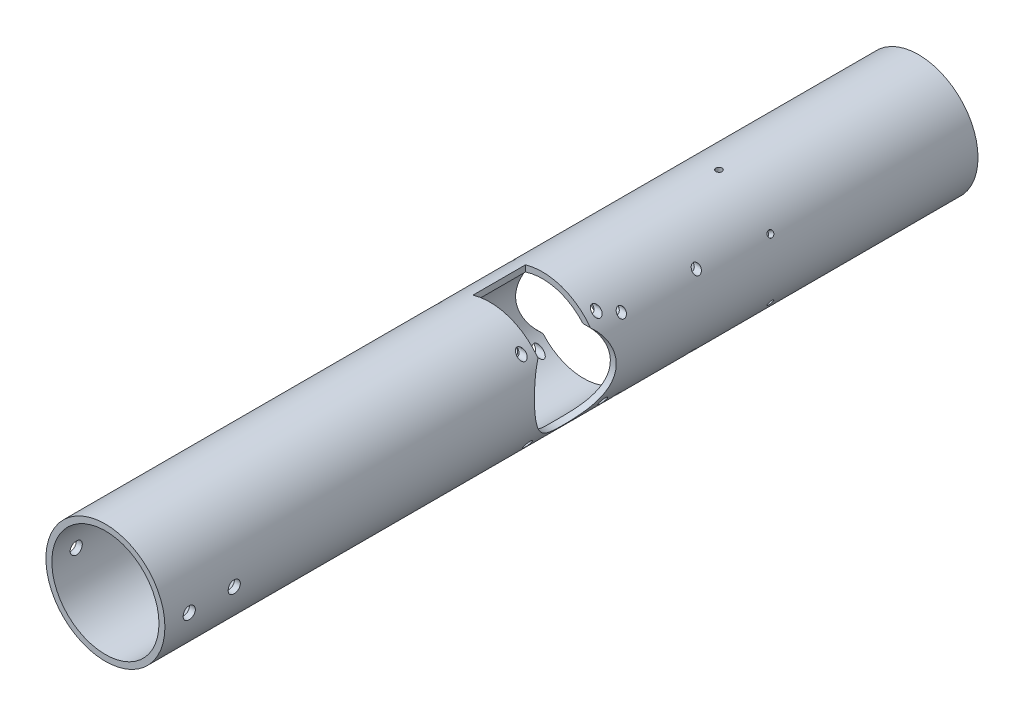
SolidWorks part; units mm, degrees
material "6061-T6 (SS)"
ref_plane "Front Plane" through (0, 0, 0) normal (0, 0, 1) x (1, 0, 0)
ref_plane "Top Plane" through (0, 0, 0) normal (0, 1, 0) x (1, 0, 0)
ref_plane "Right Plane" through (0, 0, 0) normal (1, 0, 0) x (0, 0, -1)
sketch "Sketch1" plane through (0, 0, 0) normal (0, 0, 1) x (1, 0, 0)
  circle A0 centre (0, 0) radius 31.75
  circle A1 centre (0, 0) radius 28.575
  dimension "D1" = 63.5
  dimension "D2" = 57.15
extrude "Boss-Extrude1" add sketch "Sketch1" along normal blind 125 and the other way blind 250 contours A1 | A0
sketch "Sketch2" plane through (0, 0, 0) normal (1, 0, 0) x (0, 0, -1)
  circle A2 centre (73.488, -2) radius 21.75
  dimension "D1" = 43.5
  dimension "D2" = 73.488
  dimension "D3" = 2
extrude "Cut-Extrude1" cut sketch "Sketch2" against normal through all
sketch "Sketch3" plane through (0, 0, 0) normal (1, 0, 0) x (0, 0, -1)
  circle A1 centre (23.45, 2) radius 21.75
  dimension "D1" = 23.45
  dimension "D2" = 43.5
  dimension "D3" = 2
extrude "Cut-Extrude2" cut sketch "Sketch3" along normal through all
sketch "Sketch5" plane through (0, 0, 0) normal (1, 0, 0) x (0, 0, -1)
  line L1 (87.488, -12.75) -> (59.488, -12.75)
  line L2 (87.488, -12.75) -> (87.488, -34.75)
  line L3 (87.488, -34.75) -> (59.488, -34.75)
  line L4 (59.488, -12.75) -> (59.488, -34.75)
  line L5 (87.488, -12.75) -> (59.488, -34.75) construction
  line L6 (87.488, -34.75) -> (59.488, -12.75) construction
  circle A0 centre (73.488, -2) radius 21.75 construction
  circle A1 centre (73.488, -2) radius 21.75 construction
  circle A2 centre (73.488, -2) radius 21.75 construction
  point P0 (73.488, -23.75)
  dimension "D1" = 28
  dimension "D2" = 22
extrude "Cut-Extrude4" cut sketch "Sketch5" against normal through all from offset 9
sketch "Sketch6" plane through (0, 0, 0) normal (1, 0, 0) x (0, 0, -1)
  line L1 (9.45, 34.75) -> (37.45, 34.75)
  line L2 (9.45, 34.75) -> (9.45, 12.75)
  line L3 (9.45, 12.75) -> (37.45, 12.75)
  line L4 (37.45, 34.75) -> (37.45, 12.75)
  line L5 (9.45, 34.75) -> (37.45, 12.75) construction
  line L6 (9.45, 12.75) -> (37.45, 34.75) construction
  circle A0 centre (23.45, 2) radius 21.75 construction
  circle A1 centre (23.45, 2) radius 21.75 construction
  circle A2 centre (23.45, 2) radius 21.75 construction
  point P0 (23.45, 23.75)
  dimension "D1" = 28
  dimension "D2" = 22
extrude "Cut-Extrude5" cut sketch "Sketch6" along normal through all from offset 9 offset against normal yes
sketch "Sketch10" plane through (0, 0, 0) normal (1, 0, 0) x (0, 0, -1)
  line L1 (113.488, 38) -> (33.488, 38)
  line L2 (113.488, 38) -> (113.488, -42)
  line L3 (113.488, -42) -> (33.488, -42)
  line L4 (33.488, 38) -> (33.488, -42)
  line L5 (113.488, 38) -> (33.488, -42) construction
  line L6 (113.488, -42) -> (33.488, 38) construction
  point P0 (73.488, -2)
  dimension "D1" = 80
  dimension "D2" = 80
sketch "Sketch11" plane through (0, 0, 0) normal (1, 0, 0) x (0, 0, -1)
  line L0 (113.488, 38) -> (33.488, -42) construction
  line L1 (113.488, -42) -> (33.488, 38) construction
  line L2 (51.738, -2) -> (95.238, -2) construction
  line L3 (53.488, 18) -> (53.488, -22) construction
  circle A0 centre (93.488, 18) radius 2
  circle A1 centre (53.488, 18) radius 2
  circle A2 centre (53.488, -22) radius 2
  circle A3 centre (93.488, -22) radius 2
  arc A4 (87.488, -18.6452) -> (59.488, -18.6452) centre (73.488, -2) ccw construction
  arc A5 (87.488, -18.6452) -> (59.488, -18.6452) centre (73.488, -2) ccw construction
  point P18 (53.488, -2)
  dimension "D5" = 4
  dimension "D1" = 40
extrude "Cut-Extrude8" cut sketch "Sketch11" against normal through all both and the other way through all
sketch "Sketch12" plane through (0, 0, 0) normal (1, 0, 0) x (0, 0, -1)
  line L0 (-125, 31.75) -> (-125, -31.75) construction
  circle A0 centre (-112, 0) radius 3.25
  circle A1 centre (-88, 0) radius 3.25
  dimension "D2" = 6.5
  dimension "D3" = 24
  dimension "D4" = 13
extrude "Cut-Extrude10" cut sketch "Sketch12" against normal through all both and the other way through all
sketch "Sketch13" plane through (0, 0, 0) normal (0, 1, 0) x (1, 0, 0)
  line L0 (0, -34.925) -> (0, 34.925) construction
  line L1 (28.575, 250) -> (-28.575, 250) construction
  line L2 (0, 250) -> (0, -125) construction
  circle A0 centre (0, 238) radius 2.25 construction
  circle A1 centre (0, 205.9) radius 2.25 construction
  dimension "D2" = 4.5
  dimension "D3" = 32.1
  dimension "D1" = 12
sketch "Sketch14" plane through (0, 0, 0) normal (1, 0, 0) x (0, 0, -1)
  line L0 (3.45, -18) -> (3.45, 22) construction
  line L1 (-1.55, 27) -> (48.45, 27) construction
  line L2 (-1.55, 27) -> (-1.55, -23) construction
  line L3 (-1.55, -23) -> (48.45, -23) construction
  line L4 (48.45, 27) -> (48.45, -23) construction
  line L5 (-1.55, 27) -> (48.45, -23) construction
  line L6 (-1.55, -23) -> (48.45, 27) construction
  circle A0 centre (3.45, 22) radius 2
  circle A1 centre (43.45, 22) radius 2
  circle A2 centre (43.45, -18) radius 2
  circle A3 centre (3.45, -18) radius 2
  point P0 (23.45, 2)
  point P14 (3.45, 2)
  dimension "D5" = 4
  dimension "D1" = 40
  dimension "D2" = 50
sketch "Sketch15" plane through (0, 0, 0) normal (1, 0, 0) x (0, 0, -1)
  circle A0 centre (3.45, 22) radius 2
  circle A1 centre (43.45, 22) radius 2
  circle A2 centre (43.45, -18) radius 2
  circle A3 centre (3.45, -18) radius 2
  dimension "D1" = 4
extrude "Cut-Extrude12" cut sketch "Sketch15" against normal through all and the other way through all
hole_wizard "M4 Clearance Hole1" positions "Sketch18" profile "Sketch19" hole size "M4" standard "ANSI Metric"
sketch "Sketch18" plane through (0, 0, 0) normal (1, 0, 0) x (0, 0, -1)
  circle A0 centre (3.45, 22) radius 2 construction
  circle A1 centre (43.45, 22) radius 2 construction
  circle A2 centre (3.45, -18) radius 2 construction
  circle A3 centre (43.45, -18) radius 2 construction
  point P0 (3.45, 22)
  point P2 (43.45, 22)
  point P4 (3.45, -18)
  point P6 (43.45, -18)
  point P20 (93.488, 18)
  point P23 (53.488, 18)
  point P26 (93.488, -22)
  point P29 (53.488, -22)
sketch "Sketch19" plane through (0, 22, -3.45) normal (0, 1, 0) x (0, 0, 1)
  line L0 (0, 0) -> (0, 31.75)
  line L1 (0, 31.75) -> (2.25, 31.75)
  line L2 (2.25, 31.75) -> (2.25, 0)
  line L5 (2.25, 0) -> (0, 0)
  line L11 (0, -6.35) -> (0, 107.95) construction
  dimension "Thru Hole Dia." = 4.5
  dimension "Thru Hole Depth" = 31.75
mirror "Mirror1" about plane through (0, 0, 0) normal (1, 0, 0) of "M4 Clearance Hole1"
sketch "Sketch21" plane through (0, 0, -250) normal (0, 0, -1) x (-1, 0, 0)
  circle A0 centre (0, 0) radius 30
  dimension "D1" = 60
extrude "Cut-Extrude14" cut sketch "Sketch21" against normal blind 7
sketch "Sketch22" plane through (0, 0, 0) normal (1, 0, 0) x (0, 0, -1)
  line L0 (250, -31.75) -> (250, 31.75) construction
  line L1 (250, -31.75) -> (250, 31.75) construction
  circle A0 centre (221.65, 0) radius 2.25 construction
  circle A1 centre (131.65, 0) radius 2.25 construction
  circle A2 centre (115.3, 0) radius 2.25
  circle A4 centre (238, 0) radius 2.25 construction
  point P14 (250, 0)
  dimension "D1" = 134.7
  dimension "D4" = 12
  dimension "D5" = 4.5
  dimension "D2" = 118.35
  dimension "D3" = 28.35
extrude "Cut-Extrude15" [suppressed] cut sketch "Sketch22" along normal through all
sketch "Sketch23" plane through (0, 0, -243) normal (0, 0, -1) x (-1, 0, 0)
  circle A0 centre (0, 0) radius 28.575 construction
  circle A1 centre (0, 0) radius 30
  circle A2 centre (0, 0) radius 30
  circle A3 centre (0, 0) radius 28.575
  dimension "D1" = 0
extrude "Boss-Extrude2" add sketch "Sketch23" along normal up to surface (7 mm away) up to face at (-30, 0, -250)
pattern_circular "CirPattern2" [suppressed] count 4 over 360
ref_plane "Plane1" through (0, 0, 75) normal (0, 0, 1) x (1, 0, 0)
split "Split1" trim tools "Plane1" bodies to split 124 resulting bodies 125 126
move or copy body "Body-Move/Copy1" bodies to move or copy 125 copy no translate (0, 0, 70.65) parameters "D1"=0, "D2"=0, "D3"=70.65
sketch "Sketch24" plane through (0, 0, 75) normal (0, 0, 1) x (1, 0, 0)
  circle A0 centre (0, 0) radius 28.575 construction
  circle A1 centre (0, 0) radius 31.75
  circle A2 centre (0, 0) radius 31.75
  circle A3 centre (0, 0) radius 28.575
  dimension "D1" = 0
extrude "Boss-Extrude3" add sketch "Sketch24" along normal up to surface (70.65 mm away) up to face at (31.75, 0, 145.65)
sketch "Sketch25" plane through (0, 0, -250) normal (0, 0, -1) x (-1, 0, 0)
  circle A0 centre (0, 0) radius 31.75 construction
  circle A1 centre (0, 0) radius 31.75
extrude "Cut-Extrude16" cut sketch "Sketch25" against normal blind 1
ref_plane "Plane2" through (0, 0, -126.65) normal (0, 0, -1) x (-1, 0, 0)
sketch "Sketch26" plane through (0, 0, -126.65) normal (0, 0, -1) x (-1, 0, 0)
  circle A0 centre (0, 0) radius 34.1
  circle A1 centre (0, 0) radius 31.75 construction
  circle A2 centre (0, 0) radius 31.75
  dimension "D1" = 68.2
extrude "Boss-Extrude4" [suppressed] add sketch "Sketch26" along normal blind 10
sketch "Sketch29" plane through (0, 0, -249) normal (0, 0, -1) x (-1, 0, 0)
  circle A0 centre (0, 0) radius 21
  circle A1 centre (0, 0) radius 28.575 construction
  circle A2 centre (0, 0) radius 28.575
  dimension "D1" = 42
extrude "Boss-Extrude5" [suppressed] add sketch "Sketch29" against normal blind 10
sketch "Sketch27" plane through (0, 0, -249) normal (0, 0, -1) x (-1, 0, 0)
  line L0 (2.25, 0) -> (-2.25, 0) construction
  circle A0 centre (0, 0) radius 24.75 construction
  point P4 (0, 24.75)
  dimension "D1" = 49.5
hole_wizard "M4x0.7 Tapped Hole1" [suppressed] positions "Sketch27" profile "Sketch31" tap size "M4x0.7" standard "ANSI Metric"
sketch "Sketch31" plane through (0, 24.75, -249) normal (1, 0, 0) x (0, 1, 0)
  line L0 (0, 0) -> (0, 444.65)
  line L1 (0, 444.65) -> (1.65, 444.65)
  line L2 (1.65, 444.65) -> (1.65, 0)
  line L5 (1.65, 0) -> (0, 0)
  line L11 (0, -6.35) -> (0, 107.95) construction
  dimension "Thru Tap Drill Dia." = 3.3
  dimension "Thru Tap Drill Depth" = 444.65
cosmetic thread "Hole Thread1" [suppressed] parameters "D2"=4
pattern_circular "CirPattern3" [suppressed] count 8 over 360
cosmetic thread "Hole Thread2" [suppressed] parameters "D2"=4
cosmetic thread "Hole Thread3" [suppressed] parameters "D2"=4
cosmetic thread "Hole Thread4" [suppressed] parameters "D2"=4
cosmetic thread "Hole Thread5" [suppressed] parameters "D2"=4
cosmetic thread "Hole Thread6" [suppressed] parameters "D2"=4
cosmetic thread "Hole Thread7" [suppressed] parameters "D2"=4
cosmetic thread "Hole Thread8" [suppressed] parameters "D2"=4
sketch "Sketch32" plane through (0, 0, -249) normal (0, 0, -1) x (-1, 0, 0)
  circle A0 centre (0, 0) radius 28.575 construction
  circle A1 centre (0, 0) radius 31.75
  circle A2 centre (0, 0) radius 31.75
  circle A3 centre (0, 0) radius 28.575
  dimension "D1" = 0
extrude "Cut-Extrude17" cut sketch "Sketch32" against normal blind 10
sketch "Sketch34" plane through (0, 0, 0) normal (1, 0, 0) x (0, 0, -1)
  line L0 (238.134, 31.75) -> (239, 30.25)
  line L1 (239, 31.75) -> (37.45, 31.75) construction
  line L2 (239, -31.75) -> (239, 31.75) construction
  line L3 (239, 30.25) -> (239, 31.75)
  line L4 (239, 31.75) -> (238.134, 31.75)
  dimension "D1" = 1.5
  dimension "D2" = 30
revolve "Cut-Revolve1" cut sketch "Sketch34" angle 360 about axis through (0, 0, -250) along (0, 0, 1)
sketch "Sketch35" plane through (0, 0, 0) normal (0, 1, 0) x (1, 0, 0)
  line L0 (30.25, 239) -> (-30.25, 239) construction
  point P0 (0, 131.65)
  point P1 (0, 0)
  dimension "D1" = 107.35
hole_wizard "M4x0.7 Tapped Hole2" positions "Sketch35" profile "Sketch36" tap size "M4x0.7" standard "ANSI Metric"
sketch "Sketch36" plane through (0, 0, -131.65) normal (1, 0, 0) x (0, 0, -1)
  line L0 (0, 0) -> (0, 31.75)
  line L1 (0, 31.75) -> (1.65, 31.75)
  line L2 (1.65, 31.75) -> (1.65, 0)
  line L5 (1.65, 0) -> (0, 0)
  line L11 (0, -6.35) -> (0, 107.95) construction
  dimension "Thru Tap Drill Dia." = 3.3
  dimension "Thru Tap Drill Depth" = 31.75
cosmetic thread "Hole Thread9" parameters "D2"=4
pattern_circular "CirPattern4" count 6 over 360 about axis through (0, 0, -250) along (0, 0, 1) of "M4x0.7 Tapped Hole2"
cosmetic thread "Hole Thread10" parameters "D2"=4
cosmetic thread "Hole Thread11" parameters "D2"=4
cosmetic thread "Hole Thread12" parameters "D2"=4
cosmetic thread "Hole Thread13" parameters "D2"=4
cosmetic thread "Hole Thread14" parameters "D2"=4
